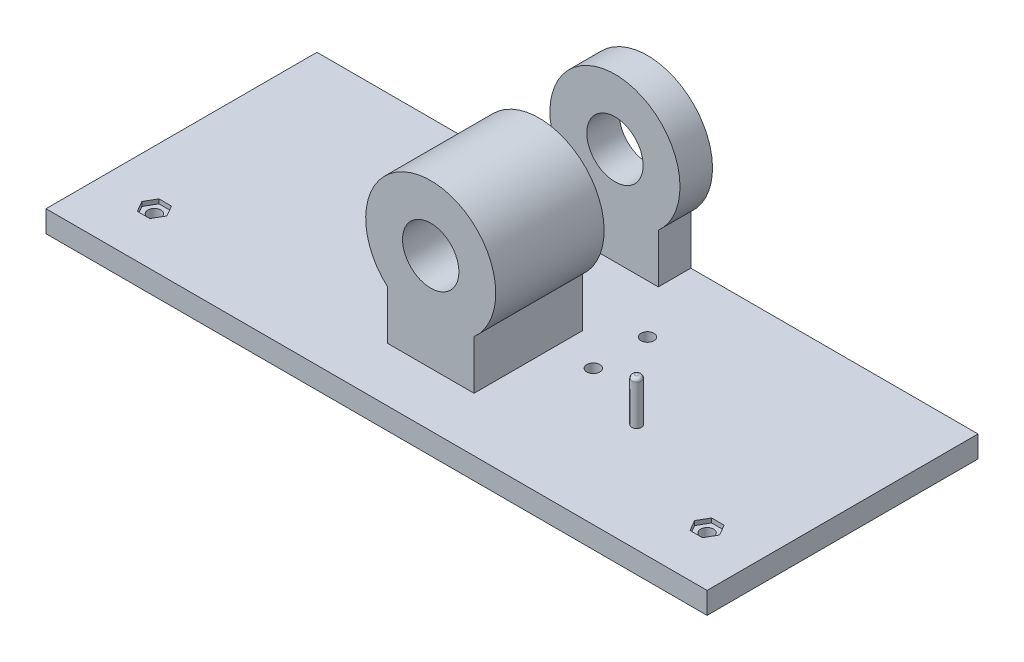
SolidWorks part; units mm, degrees
ref_plane "Front Plane" through (0, 0, 0) normal (0, 0, 1) x (1, 0, 0)
ref_plane "Top Plane" through (0, 0, 0) normal (0, 1, 0) x (1, 0, 0)
ref_plane "Right Plane" through (0, 0, 0) normal (1, 0, 0) x (0, 0, -1)
sketch "Sketch1" plane through (0, 0, 0) normal (0, 1, 0) x (1, 0, 0)
  line L0 (152.5, 125) -> (152.5, 0) construction
  line L1 (0, 0) -> (305, 0)
  line L2 (0, 0) -> (0, 125)
  line L3 (0, 125) -> (305, 125)
  line L4 (305, 0) -> (305, 125)
  line L5 (25, 100) -> (280, 100) construction
  line L6 (280, 25) -> (280, 100) construction
  line L7 (25, 25) -> (280, 25) construction
  line L8 (25, 25) -> (25, 100) construction
  line L9 (152.5, 62.5) -> (25, 62.5) construction
  line L10 (30.7735, 100) -> (27.8868, 105) construction
  line L11 (27.8868, 105) -> (22.1132, 105) construction
  line L12 (22.1132, 105) -> (19.2265, 100) construction
  line L13 (19.2265, 100) -> (22.1132, 95) construction
  line L14 (22.1132, 95) -> (27.8868, 95) construction
  line L15 (27.8868, 95) -> (30.7735, 100) construction
  line L16 (27.8868, 30) -> (30.7735, 25) construction
  line L17 (22.1132, 30) -> (27.8868, 30) construction
  line L18 (19.2265, 25) -> (22.1132, 30) construction
  line L19 (22.1132, 20) -> (19.2265, 25) construction
  line L20 (27.8868, 20) -> (22.1132, 20) construction
  line L21 (30.7735, 25) -> (27.8868, 20) construction
  line L22 (282.8868, 30) -> (277.1132, 30) construction
  line L23 (285.7735, 25) -> (282.8868, 30) construction
  line L24 (282.8868, 20) -> (285.7735, 25) construction
  line L25 (277.1132, 20) -> (282.8868, 20) construction
  line L26 (274.2265, 25) -> (277.1132, 20) construction
  line L27 (277.1132, 30) -> (274.2265, 25) construction
  line L28 (277.1132, 95) -> (274.2265, 100) construction
  line L29 (282.8868, 95) -> (277.1132, 95) construction
  line L30 (285.7735, 100) -> (282.8868, 95) construction
  line L31 (282.8868, 105) -> (285.7735, 100) construction
  line L32 (277.1132, 105) -> (282.8868, 105) construction
  line L33 (274.2265, 100) -> (277.1132, 105) construction
  line L34 (172.5, 75) -> (172.5, 125) construction
  line L35 (132.5, 0) -> (172.5, 0) construction
  line L36 (132.5, 0) -> (132.5, 125) construction
  line L37 (132.5, 125) -> (172.5, 125) construction
  line L38 (172.5, 0) -> (172.5, 125) construction
  line L39 (132.5, 75) -> (172.5, 75) construction
  line L40 (132.5, 75) -> (132.5, 25) construction
  line L41 (132.5, 25) -> (172.5, 25) construction
  line L42 (172.5, 75) -> (172.5, 25) construction
  line L43 (172.5, 75) -> (190, 62.5) construction
  line L48 (190, 62.5) -> (190, 75) construction
  line L49 (190, 75) -> (172.5, 75) construction
  line L50 (190, 62.5) -> (190, 75) construction
  line L51 (190, 75) -> (190, 87.5) construction
  circle A1 centre (25, 100) radius 5 construction
  circle A3 centre (280, 25) radius 3
  circle A4 centre (25, 25) radius 3
  circle A5 centre (190, 62.5) radius 3
  circle A7 centre (190, 87.5) radius 3
  dimension "D3" = 6
  dimension "D7" = 6
  dimension "D1" = 305
  dimension "D2" = 125
  dimension "D5" = 10
  dimension "D6" = 40
  dimension "D8" = 50
  dimension "D9" = 12.5
  dimension "D10" = 17.5
  dimension "D4" = 25
  dimension "D11" = 2
extrude "Boss-Extrude1" add sketch "Sketch1" along normal blind 10
sketch "Sketch6" plane through (0, 10, 0) normal (0, 1, 0) x (1, 0, 0)
  line L0 (152.5, 125) -> (152.5, 0) construction
  line L7 (305, 125) -> (0, 125) construction
  line L8 (0, 0) -> (305, 0) construction
  line L9 (152.5, 62.5) -> (0, 62.5) construction
  line L10 (0, 125) -> (0, 0) construction
  line L29 (27.8868, 30) -> (30.7735, 25)
  line L30 (274.2265, 25) -> (277.1132, 20)
  line L31 (277.1132, 20) -> (282.8868, 20)
  line L32 (282.8868, 20) -> (285.7735, 25)
  line L33 (285.7735, 25) -> (282.8868, 30)
  line L34 (282.8868, 30) -> (277.1132, 30)
  line L35 (277.1132, 30) -> (274.2265, 25)
  line L36 (22.1132, 30) -> (27.8868, 30)
  line L37 (19.2265, 25) -> (22.1132, 30)
  line L38 (22.1132, 20) -> (19.2265, 25)
  line L39 (27.8868, 20) -> (22.1132, 20)
  line L40 (30.7735, 25) -> (27.8868, 20)
  circle A0 centre (280, 25) radius 5 construction
  dimension "D1" = 10
extrude "Cut-Extrude1" cut sketch "Sketch6" against normal blind 2
sketch "Sketch7" plane through (0, 10, 0) normal (0, 1, 0) x (1, 0, 0)
  line L0 (0, 0) -> (305, 0) construction
  line L1 (132.5, 25) -> (172.5, 25)
  line L2 (132.5, 25) -> (132.5, 75)
  line L3 (132.5, 75) -> (172.5, 75)
  line L4 (172.5, 25) -> (172.5, 75)
  line L5 (152.5, 0) -> (152.5, 125) construction
  line L6 (305, 125) -> (0, 125) construction
  line L7 (172.5, 75) -> (172.5, 125) construction
  line L18 (132.5, 110) -> (172.5, 110)
  line L19 (132.5, 110) -> (132.5, 125)
  line L20 (132.5, 125) -> (172.5, 125)
  line L21 (172.5, 110) -> (172.5, 125)
  point P11 (152.5, 75)
  point P20 (152.5, 110)
  dimension "D1" = 40
  dimension "D2" = 50
  dimension "D4" = 15
extrude "Boss-Extrude2" add sketch "Sketch7" along normal blind 22.6393
sketch "Sketch11" plane through (0, 0, -25) normal (0, 0, 1) x (1, 0, 0)
  circle A0 centre (152.5, 55) radius 30
  circle A1 centre (152.5, 55) radius 13
  dimension "D1" = 60
  dimension "D2" = 26
extrude "Boss-Extrude3" add sketch "Sketch11" against normal up to surface (100 mm away) up to face at (152.5, 13.1598, -125)
ref_plane "Plane1" through (0, 0, -62.5) normal (0, 0, 1) x (1, 0, 0)
sketch "Sketch12" plane through (305, 0, 0) normal (1, 0, 0) x (0, 0, -1)
  line L0 (125, 85) -> (25, 85) construction
  line L1 (75, 10) -> (110, 10)
  line L2 (75, 10) -> (75, 85)
  line L3 (75, 85) -> (110, 85)
  line L4 (110, 10) -> (110, 85)
  line L6 (110, 32.6393) -> (110, 10) construction
extrude "Cut-Extrude2" cut sketch "Sketch12" against normal through all
sketch "Sketch13" plane through (0, 10, 0) normal (0, 1, 0) x (1, 0, 0)
  line L0 (222.5, 50) -> (172.5, 50) construction
  line L1 (172.5, 25) -> (172.5, 75) construction
  circle A0 centre (222.5, 50) radius 2.25
  dimension "D1" = 4.5
  dimension "D2" = 50
extrude "Boss-Extrude4" add sketch "Sketch13" along normal blind 20
fillet "Fillet1" radius 1.5 1 edges at (222.5, 30, -47.75)
equation "\"joint_width\"=4"
equation "\"D2@Sketch7\"=5"
equation "\"short_base_length\"=12.5"
equation "\"D2@Sketch1\"=\"short_base_length\""
equation "\"outer_diam_main_joint\"=6"
equation "\"D1@Sketch11\"=\"outer_diam_main_joint\""
equation "\"D1@Sketch7\"=\"outer_diam_main_joint\"-2"
equation "\"D1@Boss-Extrude2\"=(\"outer_diam_main_joint\"/2)+1.5cm-sqr((\"outer_diam_main_joint\"/2)^2-((\"outer_diam_main_joint\"-2)/2)^2)"
equation "\"D6@Sketch1\"=\"outer_diam_main_joint\"-2"
equation "\"pulleyside\"=1.5"
